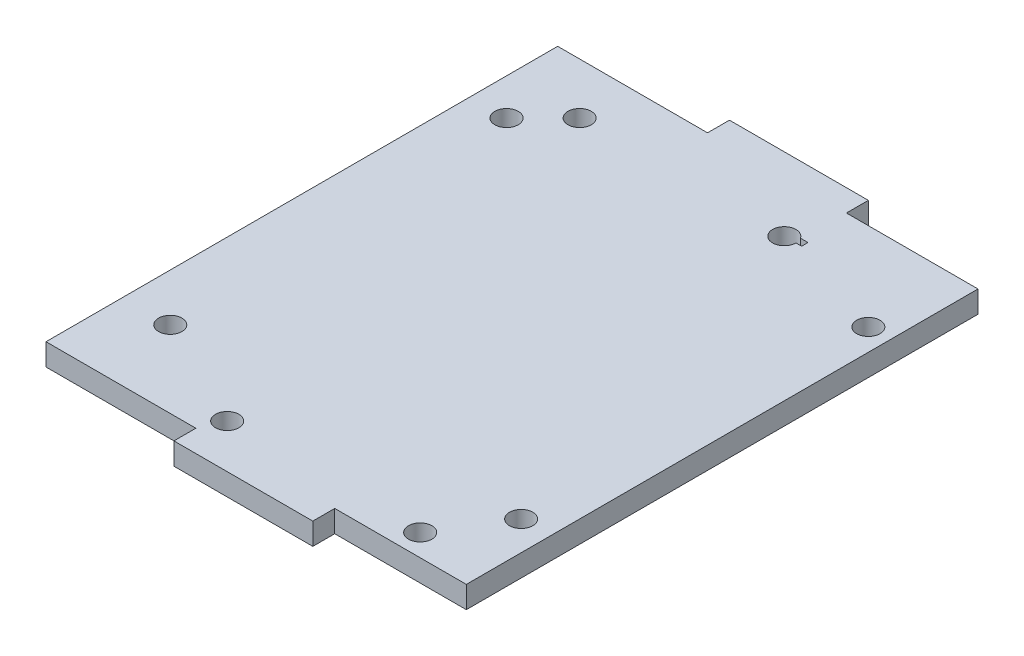
SolidWorks part; units mm, degrees
ref_plane "Front Plane" through (0, 0, 0) normal (0, 0, 1) x (1, 0, 0)
ref_plane "Top Plane" through (0, 0, 0) normal (0, 1, 0) x (1, 0, 0)
ref_plane "Right Plane" through (0, 0, 0) normal (1, 0, 0) x (0, 0, -1)
sketch "Sketch1" plane through (0, 0, 0) normal (0, 1, 0) x (1, 0, 0)
  line L0 (63.7979, -35) -> (63.7979, 35)
  line L1 (8.7979, 35) -> (6.2979, 35)
  line L2 (6.2979, 35) -> (6.2979, -35)
  line L3 (6.2979, -35) -> (8.7979, -35)
  line L5 (45.8979, 28) -> (46.6681, 28)
  line L7 (8.7979, 35) -> (26.7979, 35)
  line L8 (26.7979, 35) -> (26.7979, 38)
  line L9 (26.7979, 38) -> (45.7979, 38)
  line L10 (45.7979, 38) -> (45.7979, 35)
  line L11 (45.7979, 35) -> (63.7979, 35)
  line L12 (45.6375, 28.8749) -> (46.6681, 28.8749)
  line L13 (0, 0) -> (58, 0) construction
  line L14 (46.6681, 28) -> (46.6681, 28.8749)
  line L18 (61, -35) -> (63.7979, -35)
  line L19 (61, 35) -> (63.7979, 35)
  line L25 (36.2979, -34.5) -> (36.2979, 34.5) construction
  line L31 (9.2979, 34.5) -> (63.2979, -34.5) construction
  line L32 (9.2979, -34.5) -> (63.2979, 34.5) construction
  line L37 (61, -35) -> (63.7979, -35)
  line L38 (45.7979, -35) -> (63.7979, -35)
  line L39 (45.7979, -38) -> (45.7979, -35)
  line L40 (26.7979, -38) -> (45.7979, -38)
  line L41 (26.7979, -35) -> (26.7979, -38)
  line L42 (8.7979, -35) -> (26.7979, -35)
  circle A0 centre (12.7979, -24.5) radius 1.6
  circle A1 centre (59.7979, -23.5) radius 1.6
  circle A2 centre (16.2979, 28) radius 1.6
  arc A3 (45.6375, 28.8749) -> (45.8979, 28) centre (44.2979, 28) ccw
  point P29 (36.2979, 0)
  dimension "D14" = 3.2
  dimension "D17" = 3.2
  dimension "D18" = 3.2
  dimension "D19" = 3.2
  dimension "D8" = 28
  dimension "D3" = 47
  dimension "D4" = 19
  dimension "D5" = 18
  dimension "D6" = 26.7979
  dimension "D7" = 18
  dimension "D9" = 52.5
  dimension "D10" = 51.5
  dimension "D11" = 3
  dimension "D12" = 69
  dimension "D13" = 7
  dimension "D15" = 2.5
  dimension "D16" = 3.5
  dimension "D23" = 19
extrude "Boss-Extrude1" add sketch "Sketch1" along normal blind 3 contours L42 L41 L40 L39 L38 L18 L19 L11 L10 L9 L8 L7 | A3 A2 A1 A0 region at (35.0942, 0, 0.0208)
sketch "Sketch3" plane through (0, 0, 0) normal (0, -1, 0) x (1, 0, 0)
  line L0 (6.2979, -35) -> (6.2979, 35) construction
  line L1 (6.2979, -35) -> (26.7979, -35) construction
  line L2 (45.7979, -35) -> (63.7979, -35) construction
  circle A0 centre (11.2979, -23) radius 1.6
  circle A1 centre (60.7979, -23) radius 1.6
  circle A2 centre (54.4879, 32) radius 1.6
  circle A3 centre (28.0879, 32) radius 1.6
  dimension "D1" = 3.2
  dimension "D2" = 3.2
  dimension "D3" = 3.2
  dimension "D4" = 3.2
  dimension "D5" = 5
  dimension "D6" = 12
  dimension "D7" = 12
  dimension "D8" = 49.5
  dimension "D9" = 6.31
  dimension "D10" = 55
  dimension "D11" = 26.4
extrude "Cut-Extrude1" cut sketch "Sketch3" against normal blind 10
